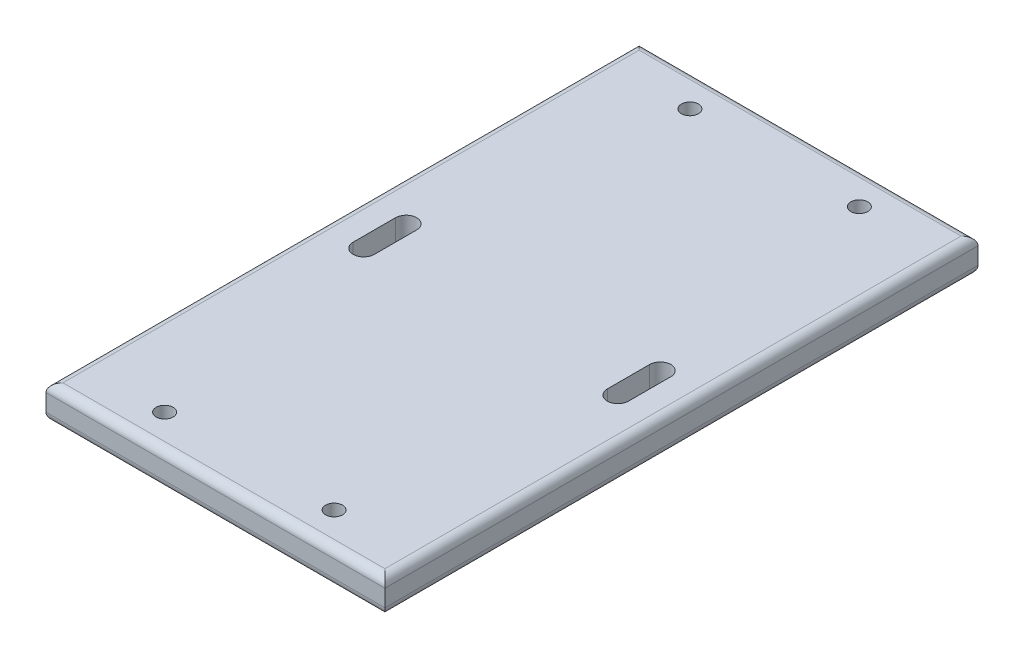
SolidWorks part; units mm, degrees
ref_plane "Front Plane" through (0, 0, 0) normal (0, 0, 1) x (1, 0, 0)
ref_plane "Top Plane" through (0, 0, 0) normal (0, 1, 0) x (1, 0, 0)
ref_plane "Right Plane" through (0, 0, 0) normal (1, 0, 0) x (0, 0, -1)
sketch "Sketch2" plane through (0, 0, 0) normal (0, 1, 0) x (1, 0, 0)
  line L0 (-40, 140) -> (-40, 0) construction
  line L1 (0, 0) -> (-80, 0)
  line L2 (0, 0) -> (0, 140)
  line L3 (0, 140) -> (-80, 140)
  line L4 (-80, 0) -> (-80, 140)
  line L5 (0, 70) -> (-80, 70) construction
  line L6 (-8, 28) -> (-8, 8) construction
  line L7 (-4, 28) -> (-4, 8)
  line L8 (-12, 28) -> (-12, 8)
  line L9 (-8, 112) -> (-8, 132) construction
  line L10 (-4, 112) -> (-4, 132)
  line L11 (-12, 112) -> (-12, 132)
  line L12 (-72, 112) -> (-72, 132) construction
  line L13 (-76, 112) -> (-76, 132)
  line L14 (-68, 112) -> (-68, 132)
  line L15 (-72, 28) -> (-72, 8) construction
  line L16 (-76, 28) -> (-76, 8)
  line L17 (-68, 28) -> (-68, 8)
  arc A0 (-4, 28) -> (-12, 28) centre (-8, 28) ccw
  arc A1 (-12, 8) -> (-4, 8) centre (-8, 8) ccw
  arc A2 (-4, 112) -> (-12, 112) centre (-8, 112) cw
  arc A3 (-12, 132) -> (-4, 132) centre (-8, 132) cw
  arc A4 (-76, 112) -> (-68, 112) centre (-72, 112) ccw
  arc A5 (-68, 132) -> (-76, 132) centre (-72, 132) ccw
  arc A6 (-76, 28) -> (-68, 28) centre (-72, 28) cw
  arc A7 (-68, 8) -> (-76, 8) centre (-72, 8) cw
  point P11 (-8, 18)
  point P16 (-4, 18)
  point P17 (0, 0)
  point P20 (-8, 122)
  point P27 (-72, 122)
  point P34 (-72, 18)
  dimension "D5" = 4
  dimension "D1" = 80
  dimension "D2" = 140
  dimension "D3" = 20
  dimension "D4" = 8
  dimension "D6" = 8
  dimension "D7" = 8
extrude "Boss-Extrude1" add sketch "Sketch2" against normal blind 5
sketch "Sketch3" plane through (0, 0, 0) normal (0, 1, 0) x (1, 0, 0)
  line L1 (-80, 0) -> (0, 0)
  line L2 (-80, 0) -> (-80, 140)
  line L3 (-80, 140) -> (0, 140)
  line L4 (0, 0) -> (0, 140)
extrude "Boss-Extrude2" add sketch "Sketch3" along normal blind 3
fillet "Fillet1" radius 2 8 edges at (-40, -5, -140) (-40, 3, -140) (-80, -5, -70) (-80, 3, -70) (0, 3, -70) (0, -5, -70) (-40, -5, 0) (-40, 3, 0)
sketch "Sketch4" plane through (0, 0, 0) normal (0, 1, 0) x (1, 0, 0)
  line L0 (-80, 70) -> (-2, 70) construction
  line L1 (-80, 140) -> (0, 140)
  line L2 (-80, 140) -> (-80, 0)
  line L3 (-80, 0) -> (0, 0)
  line L4 (0, 140) -> (0, 0)
  line L5 (0, 0) -> (-80, 0)
  line L6 (0, 0) -> (0, 140)
  line L7 (0, 140) -> (-80, 140)
  line L8 (-80, 0) -> (-80, 140)
  line L9 (-2, 2) -> (-2, 138) construction
  line L10 (-40, 140) -> (-40, 2) construction
  line L11 (-78, 2) -> (-2, 2) construction
  line L12 (-10, 75) -> (-10, 65) construction
  line L13 (-7.5, 75) -> (-7.5, 65)
  line L14 (-12.5, 75) -> (-12.5, 65)
  line L15 (-70, 75) -> (-70, 65) construction
  line L16 (-72.5, 75) -> (-72.5, 65)
  line L17 (-67.5, 75) -> (-67.5, 65)
  arc A0 (-7.5, 75) -> (-12.5, 75) centre (-10, 75) ccw
  arc A1 (-12.5, 65) -> (-7.5, 65) centre (-10, 65) ccw
  arc A2 (-72.5, 75) -> (-67.5, 75) centre (-70, 75) cw
  arc A3 (-67.5, 65) -> (-72.5, 65) centre (-70, 65) cw
  point P16 (-10, 70)
  point P21 (0, 0)
  point P22 (0, 0)
  point P25 (-70, 70)
  dimension "D1" = 10
  dimension "D2" = 5
  dimension "D3" = 8
extrude "Cut-Extrude1" cut sketch "Sketch4" against normal through all both and the other way through all contours L16 A3 L17 A2 | L14 A1 L13 A0
sketch "Sketch6" plane through (0, 3, 0) normal (0, 1, 0) x (1, 0, 0)
  line L0 (-40, 2) -> (-40, 138) construction
  line L1 (-78, 2) -> (-2, 2) construction
  line L2 (-2, 138) -> (-78, 138) construction
  line L3 (-78, 70) -> (-2, 70) construction
  line L4 (-78, 138) -> (-78, 2) construction
  line L5 (-2, 2) -> (-2, 138) construction
  line L7 (-78, 138) -> (-2, 138)
  line L8 (-78, 138) -> (-78, 2) construction
  line L9 (-78, 2) -> (-2, 2)
  line L10 (-2, 138) -> (-2, 2)
  circle A0 centre (-60, 132) radius 2
  circle A1 centre (-20, 132) radius 2
  circle A2 centre (-20, 8) radius 2
  circle A3 centre (-60, 8) radius 2
  dimension "D1" = 18
  dimension "D3" = 4
  dimension "D2" = 6
extrude "Cut-Extrude2" cut sketch "Sketch6" against normal blind 3 contours A3 | A2 | A1 | A0
